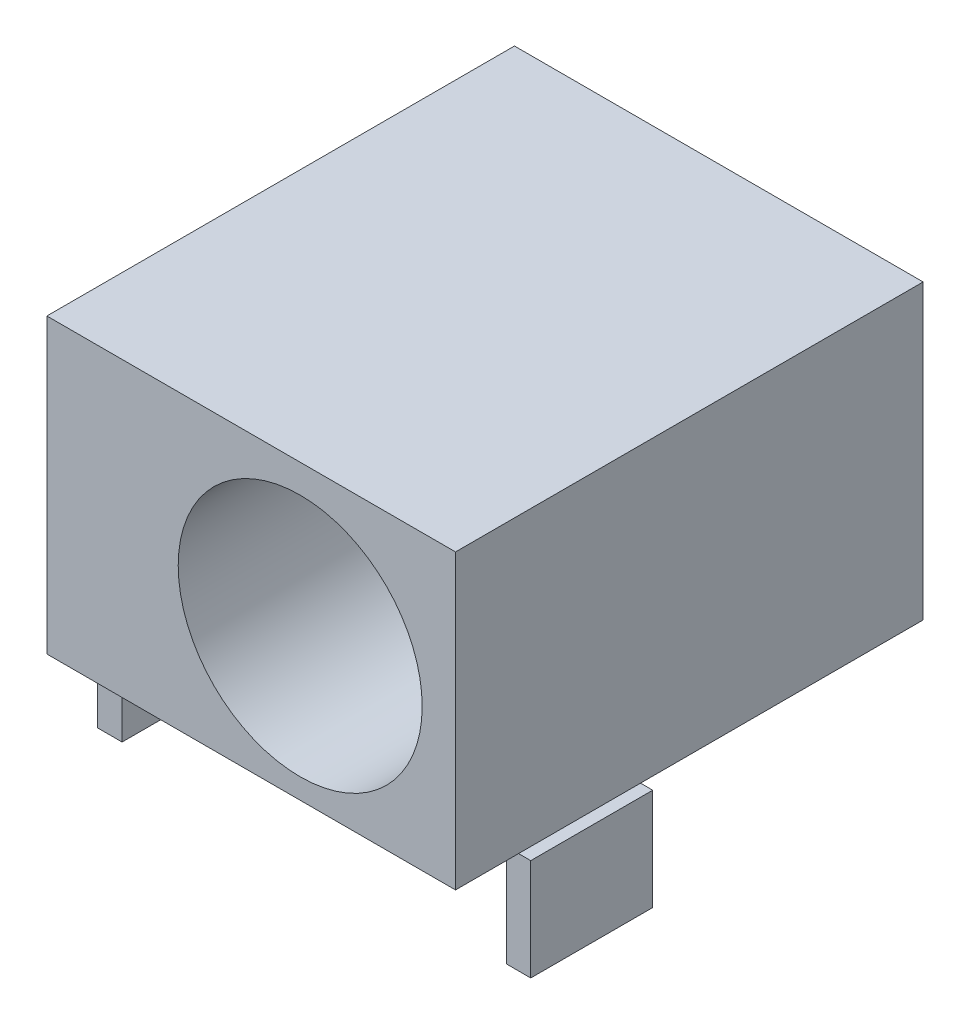
SolidWorks part; units mm, degrees
ref_plane "Front Plane" through (0, 0, 0) normal (0, 0, 1) x (1, 0, 0)
ref_plane "Top Plane" through (0, 0, 0) normal (0, 1, 0) x (1, 0, 0)
ref_plane "Right Plane" through (0, 0, 0) normal (1, 0, 0) x (0, 0, -1)
sketch "Sketch1" plane through (0, 0, 0) normal (0, 1, 0) x (1, 0, 0)
  line L0 (0, 5.75) -> (0, -5.75) construction
  line L1 (-5.025, 5.75) -> (5.025, 5.75)
  line L2 (-5.025, 5.75) -> (-5.025, -5.75)
  line L3 (-5.025, -5.75) -> (5.025, -5.75)
  line L4 (5.025, 5.75) -> (5.025, -5.75)
  line L5 (4.725, -1.2) -> (5.325, -1.2)
  line L6 (4.725, -1.2) -> (4.725, -4.2)
  line L7 (4.725, -4.2) -> (5.325, -4.2)
  line L8 (5.325, -1.2) -> (5.325, -4.2)
  line L9 (-4.725, -4.2) -> (-5.325, -4.2)
  line L10 (-4.725, -1.2) -> (-4.725, -4.2)
  line L11 (-5.325, -1.2) -> (-5.325, -4.2)
  line L12 (-4.725, -1.2) -> (-5.325, -1.2)
  point P4 (0, 5.75)
  point P6 (5.025, 0)
  point P11 (5.325, -2.7)
  point P12 (5.025, -1.2)
  dimension "D1" = 11.5
  dimension "D2" = 10.05
  dimension "D3" = 0.6
  dimension "D4" = 3
  dimension "D5" = 3.05
extrude "Boss-Extrude1" add sketch "Sketch1" against normal blind 2.5 contours L2 L12 L11 L9 | L10 L12 L2 L9 | L6 L7 L4 L5 | L8 L5 L4 L7 region at (-4.875, 0, 2.7) region at (-5.175, 0, 2.7) region at (5.175, 0, 2.7) region at (4.875, 0, 2.7)
extrude "Boss-Extrude2" add sketch "Sketch1<3>" along normal blind 7.2 contours L1 L0 L3 L4 L7 L6 L5 | L0 L1 L2 L12 L10 L9 L3 | L6 L7 L4 L5 | L10 L12 L2 L9 region at (2.4751, 0, -0.0427) region at (-2.4751, 0, -0.0427) region at (-4.875, 0, 2.7) region at (4.875, 0, 2.7)
sketch "Sketch1<3>" plane through (0, 0, 0) normal (0, 1, 0) x (1, 0, 0) same geometry as "Sketch1"
sketch3d "3DSketch2"
  line L0 (-5.025, 7.2, 5.75) -> (-5.025, 0, 5.75) construction
  line L1 (-5.025, 0, 5.75) -> (5.025, 0, 5.75) construction
  circle A0 centre (1.205, 3.5, 5.75) radius 3
  point P2 (1.205, 3.5, 8.75)
  dimension "D1" = 6
  dimension "D2" = 6.23
  dimension "D3" = 3.5
extrude "Cut-Extrude1" cut sketch "3DSketch2" along direction (0, 0, -1) on the side of the normal blind 8.2
